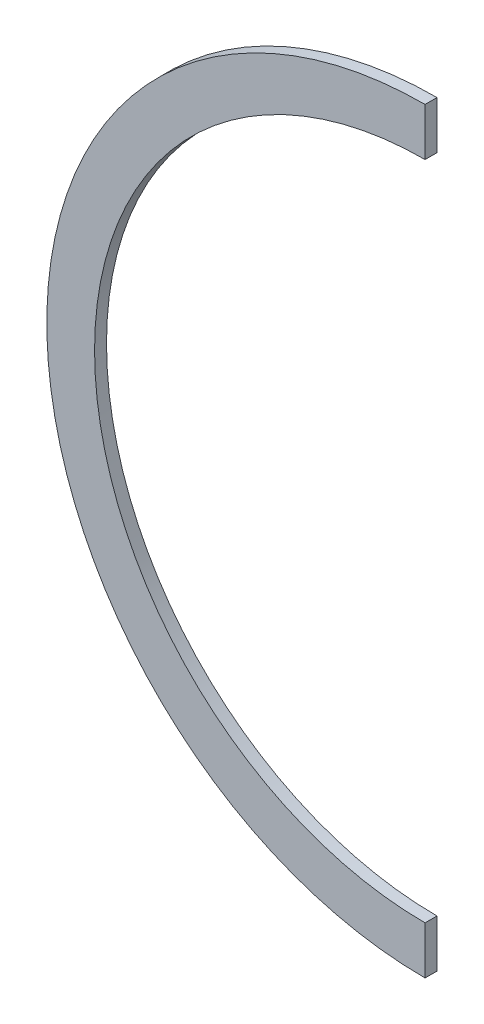
SolidWorks part; units mm, degrees
material "Balsa"
ref_plane "Front Plane" through (0, 0, 0) normal (0, 0, 1) x (1, 0, 0)
ref_plane "Top Plane" through (0, 0, 0) normal (0, 1, 0) x (1, 0, 0)
ref_plane "Right Plane" through (0, 0, 0) normal (1, 0, 0) x (0, 0, -1)
sketch "Sketch2" plane through (0, 0, 0) normal (0, 0, 1) x (1, 0, 0)
  line L0 (0, 0) -> (0, 240.9936) construction
  line L1 (-1.7839, 106.6642) -> (-1.7839, 99.822) construction
  line L2 (1.7839, 106.6642) -> (1.7839, 99.822) construction
  line L3 (-1.7839, 99.822) -> (1.7839, 99.822) construction
  line L4 (-87.7705, -42.8471) -> (-87.8712, -42.9053) construction
  line L5 (-604.1774, -338.907) -> (0, 9.8743) construction
  line L6 (-89.5483, -39.7674) -> (-83.8289, -36.4657) construction
  line L7 (-87.7705, -42.8471) -> (-82.0511, -39.5454) construction
  line L8 (-83.8289, -36.4657) -> (-82.0511, -39.5454) construction
  line L9 (604.1774, -338.907) -> (0, 9.8743) construction
  line L10 (87.7705, -42.8471) -> (82.0511, -39.5454) construction
  line L11 (87.7705, -42.8471) -> (87.8712, -42.9053) construction
  line L12 (89.5483, -39.7674) -> (83.8289, -36.4657) construction
  line L13 (83.8289, -36.4657) -> (82.0511, -39.5454) construction
  arc A0 (-7.652, 93.6463) -> (7.652, 93.6463) centre (0, 6.0782) ccw
  arc A1 (-1.7839, 106.6642) -> (-89.5483, -39.7674) centre (0, 6.0782) ccw
  arc A6 (-1.778, 93.962) -> (-7.652, 93.6463) centre (0, 6.0782) ccw
  circle A7 centre (0, 6.0782) radius 87.9018 construction
  arc A8 (0, 93.98) -> (-1.778, 93.962) centre (0, 6.0782) ccw
  arc A9 (1.778, 93.962) -> (0, 93.98) centre (0, 6.0782) ccw
  arc A10 (1.778, 93.962) -> (0, 93.98) centre (0, 6.0782) ccw construction
  arc A12 (7.652, 93.6463) -> (1.778, 93.962) centre (0, 6.0782) ccw
  arc A13 (0, 93.98) -> (-1.778, 93.962) centre (0, 6.0782) ccw construction
  arc A15 (7.652, 93.6463) -> (1.778, 93.962) centre (0, 6.0782) ccw construction
  arc A16 (-1.778, 93.962) -> (-7.652, 93.6463) centre (0, 6.0782) ccw construction
  arc A17 (0, 106.68) -> (-1.7839, 106.6642) centre (0, 6.0782) ccw
  circle A18 centre (0, 6.0782) radius 100.6018 construction
  arc A19 (1.7839, 106.6642) -> (0, 106.68) centre (0, 6.0782) ccw
  arc A20 (-87.8712, -42.9053) -> (87.8712, -42.9053) centre (0, 6.0782) ccw
  arc A21 (-89.5483, -39.7674) -> (-88.7234, -41.3442) centre (0, 6.0782) ccw
  arc A22 (-88.7234, -41.3442) -> (-87.8712, -42.9053) centre (0, 6.0782) ccw
  arc A23 (87.8712, -42.9053) -> (88.7234, -41.3442) centre (0, 6.0782) ccw
  arc A24 (89.5483, -39.7674) -> (1.7839, 106.6642) centre (0, 6.0782) ccw
  arc A25 (88.7234, -41.3442) -> (89.5483, -39.7674) centre (0, 6.0782) ccw
  point P25 (0, 99.822)
  dimension "D3" = 119.997
  dimension "D8" = 12.7
  dimension "D6" = 87.9018
  dimension "D2" = 1.7839
  dimension "D4" = 9.8743
  dimension "D5" = 3.556
  dimension "D1" = 93.98
  dimension "D7" = 5.842
  dimension "D9" = 6.604
  dimension "D10" = 3.556
extrude "Boss-Extrude1" add sketch "Sketch2" against normal blind 3.175
sketch "Sketch3" plane through (0, 0, 0) normal (1, 0, 0) x (0, 0, -1)
  line L5 (-72.4915, 152.7087) -> (76.812, 152.7087)
  line L6 (-72.4915, 152.7087) -> (-72.4915, -135.9702)
  line L7 (-72.4915, -135.9702) -> (76.812, -135.9702)
  line L8 (76.812, 152.7087) -> (76.812, -135.9702)
extrude "Cut-Extrude1" cut sketch "Sketch3" along normal through all
